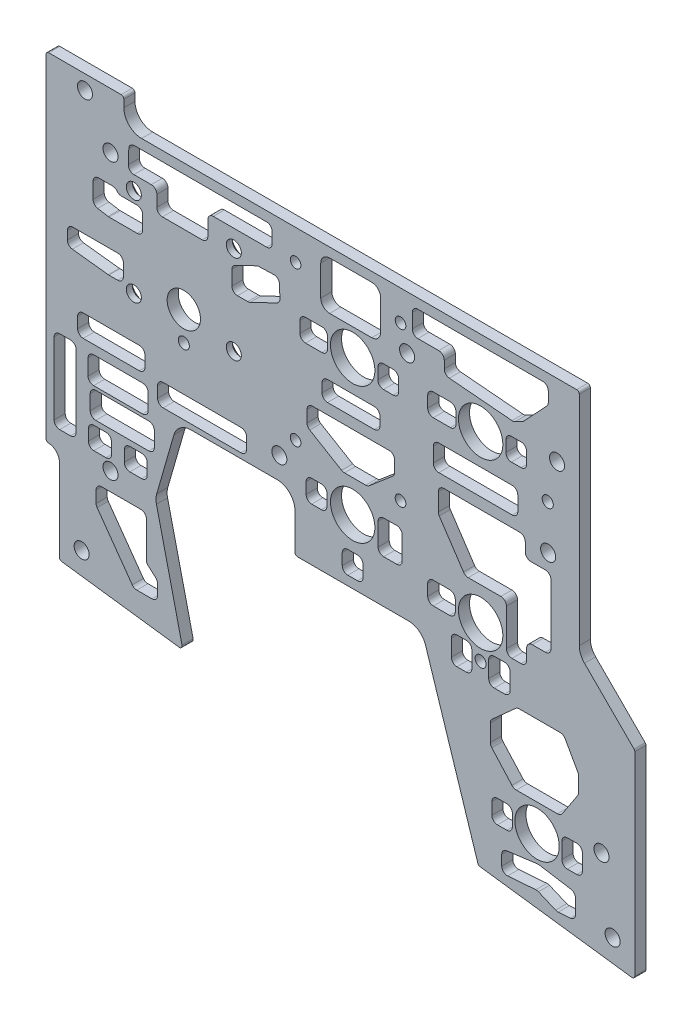
SolidWorks part; units mm, degrees
ref_plane "Front Plane" through (0, 0, 0) normal (0, 0, 1) x (1, 0, 0)
ref_plane "Top Plane" through (0, 0, 0) normal (0, 1, 0) x (1, 0, 0)
ref_plane "Right Plane" through (0, 0, 0) normal (1, 0, 0) x (0, 0, -1)
sketch "Sketch1" plane through (0, 0, 0) normal (0, 0, 1) x (1, 0, 0)
  line L16 (3.81, -91.8845) -> (3.81, -115.4033)
  line L17 (4.4725, -116.1588) -> (38.0231, -120.5758)
  line L18 (38.8645, -119.6465) -> (31.5446, -88.4134)
  line L19 (31.6093, -85.8475) -> (36.5334, -68.7608)
  line L20 (41.4148, -65.0875) -> (66.04, -65.0875)
  line L21 (71.12, -70.1675) -> (71.12, -80.518)
  line L22 (71.882, -81.28) -> (103.6122, -81.28)
  line L23 (108.4484, -84.805) -> (123.4233, -131.3792)
  line L24 (124.0493, -131.9014) -> (167.4135, -137.6104)
  line L25 (168.275, -136.8549) -> (168.275, -81.3036)
  line L26 (168.0518, -80.7647) -> (153.8879, -66.6008)
  line L27 (152.4, -63.0087) -> (152.4, -0.762)
  line L28 (151.638, 0) -> (27.305, 0)
  line L29 (22.225, 5.08) -> (22.225, 7.1755)
  line L30 (21.463, 7.9375) -> (0.762, 7.9375)
  line L31 (0, 7.1755) -> (0, -87.9495)
  line L32 (3.81, -91.8845) -> (3.81, -115.4033)
  line L33 (4.4725, -116.1588) -> (38.0231, -120.5758)
  line L34 (38.8645, -119.6465) -> (31.5446, -88.4134)
  line L35 (31.6093, -85.8475) -> (36.5334, -68.7608)
  line L36 (41.4148, -65.0875) -> (66.04, -65.0875)
  line L37 (71.12, -70.1675) -> (71.12, -80.518)
  line L38 (71.882, -81.28) -> (103.6122, -81.28)
  line L39 (108.4484, -84.805) -> (123.4233, -131.3792)
  line L40 (124.0493, -131.9014) -> (167.4135, -137.6104)
  line L41 (168.275, -136.8549) -> (168.275, -81.3036)
  line L42 (168.0518, -80.7647) -> (153.8879, -66.6008)
  line L43 (152.4, -63.0087) -> (152.4, -0.762)
  line L44 (151.638, 0) -> (27.305, 0)
  line L45 (22.225, 5.08) -> (22.225, 7.1755)
  line L46 (21.463, 7.9375) -> (0.762, 7.9375)
  line L47 (0, 7.1755) -> (0, -87.9495)
  arc A17 (3.81, -91.8845) -> (0.7374, -88.7112) centre (0.635, -91.8845) ccw
  arc A18 (3.81, -115.4033) -> (4.4725, -116.1588) centre (4.572, -115.4033) ccw
  arc A19 (38.0231, -120.5758) -> (38.8645, -119.6465) centre (38.1226, -119.8204) ccw
  arc A20 (31.6093, -85.8475) -> (31.5446, -88.4134) centre (36.4906, -87.2542) ccw
  arc A21 (41.4148, -65.0875) -> (36.5334, -68.7608) centre (41.4148, -70.1675) ccw
  arc A22 (71.12, -70.1675) -> (66.04, -65.0875) centre (66.04, -70.1675) ccw
  arc A23 (71.12, -80.518) -> (71.882, -81.28) centre (71.882, -80.518) ccw
  arc A24 (108.4484, -84.805) -> (103.6122, -81.28) centre (103.6122, -86.36) ccw
  arc A25 (123.4233, -131.3792) -> (124.0493, -131.9014) centre (124.1487, -131.1459) ccw
  arc A26 (167.4135, -137.6104) -> (168.275, -136.8549) centre (167.513, -136.8549) ccw
  arc A27 (168.275, -81.3036) -> (168.0518, -80.7647) centre (167.513, -81.3036) ccw
  arc A28 (152.4, -63.0087) -> (153.8879, -66.6008) centre (157.48, -63.0087) ccw
  arc A29 (152.4, -0.762) -> (151.638, 0) centre (151.638, -0.762) ccw
  arc A30 (22.225, 5.08) -> (27.305, 0) centre (27.305, 5.08) ccw
  arc A31 (22.225, 7.1755) -> (21.463, 7.9375) centre (21.463, 7.1755) ccw
  arc A32 (0.762, 7.9375) -> (0, 7.1755) centre (0.762, 7.1755) ccw
  arc A33 (0, -87.9495) -> (0.7374, -88.7112) centre (0.762, -87.9495) ccw
  arc A34 (3.81, -91.8845) -> (0.7374, -88.7112) centre (0.635, -91.8845) ccw
  arc A35 (3.81, -115.4033) -> (4.4725, -116.1588) centre (4.572, -115.4033) ccw
  arc A36 (38.0231, -120.5758) -> (38.8645, -119.6465) centre (38.1226, -119.8204) ccw
  arc A37 (31.6093, -85.8475) -> (31.5446, -88.4134) centre (36.4906, -87.2542) ccw
  arc A38 (41.4148, -65.0875) -> (36.5334, -68.7608) centre (41.4148, -70.1675) ccw
  arc A39 (71.12, -70.1675) -> (66.04, -65.0875) centre (66.04, -70.1675) ccw
  arc A40 (71.12, -80.518) -> (71.882, -81.28) centre (71.882, -80.518) ccw
  arc A41 (108.4484, -84.805) -> (103.6122, -81.28) centre (103.6122, -86.36) ccw
  arc A42 (123.4233, -131.3792) -> (124.0493, -131.9014) centre (124.1487, -131.1459) ccw
  arc A43 (167.4135, -137.6104) -> (168.275, -136.8549) centre (167.513, -136.8549) ccw
  arc A44 (168.275, -81.3036) -> (168.0518, -80.7647) centre (167.513, -81.3036) ccw
  arc A45 (152.4, -63.0087) -> (153.8879, -66.6008) centre (157.48, -63.0087) ccw
  arc A46 (152.4, -0.762) -> (151.638, 0) centre (151.638, -0.762) ccw
  arc A47 (22.225, 5.08) -> (27.305, 0) centre (27.305, 5.08) ccw
  arc A48 (22.225, 7.1755) -> (21.463, 7.9375) centre (21.463, 7.1755) ccw
  arc A49 (0.762, 7.9375) -> (0, 7.1755) centre (0.762, 7.1755) ccw
  arc A50 (0, -87.9495) -> (0.7374, -88.7112) centre (0.762, -87.9495) ccw
  dimension "D1" = 0
extrude "Boss-Extrude1" add sketch "Sketch1" against normal blind 3.175
hole_wizard "#6 Clearance Hole1" positions "Sketch3" profile "Sketch2" hole size "#6" standard "ANSI Inch" end condition through all
sketch "Sketch3" plane through (0, 0, -3.175) normal (0, 0, -1) x (-1, 0, 0)
  point P0 (-11.1125, 3.81)
  point P3 (-18.415, -7.9375)
  point P6 (-103.1875, -15.24)
  point P9 (-143.51, -44.45)
  point P12 (-158.75, -111.125)
  point P15 (-18.415, -86.741)
  point P18 (-66.675, -58.7375)
  point P21 (-10.16, -110.5028)
  point P25 (-146.05, -20.6375)
  point P28 (-161.925, -130.483)
sketch "Sketch2" plane through (11.1125, 3.81, -3.175) normal (1, 0, 0) x (0, 1, 0)
  line L0 (0, 0) -> (0, 3.175)
  line L1 (0, 3.175) -> (2.1526, 3.175)
  line L2 (2.1526, 3.175) -> (2.1526, 0)
  line L5 (2.1526, 0) -> (0, 0)
  line L11 (0, -6.35) -> (0, 107.95) construction
  dimension "Thru Hole Dia." = 4.3053
  dimension "Thru Hole Depth" = 3.175
sketch "Sketch4" plane through (0, 0, -3.175) normal (0, 0, -1) x (-1, 0, 0)
  circle A0 centre (-140.335, -115.57) radius 6.35
  circle A1 centre (-124.206, -71.4375) radius 6.35
  circle A2 centre (-87.63, -62.992) radius 6.35
  circle A3 centre (-87.63, -24.13) radius 6.35
  circle A4 centre (-124.206, -24.13) radius 6.35
  circle A5 centre (-124.206, -80.9625) radius 1.5875
  circle A6 centre (-39.37, -36.322) radius 4.7625
  dimension "D1" = 12.7
  dimension "D2" = 3.175
  dimension "D4" = 9.525
  dimension "D3" = 9.525
extrude "Cut-Extrude1" cut sketch "Sketch4" against normal through all
hole_wizard "CSK for #6 Flat Head Machine Screw (100)1" positions "Sketch6" profile "Sketch5" countersink size "#6" standard "ANSI Inch" end condition through all
sketch "Sketch6" plane through (0, 0, -3.175) normal (0, 0, -1) x (-1, 0, 0)
  point P0 (-53.6575, -14.097)
  point P2 (-25.0825, -14.097)
  point P4 (-25.0825, -39.497)
  point P6 (-53.6575, -39.497)
sketch "Sketch5" plane through (53.6575, -14.097, -3.175) normal (1, 0, 0) x (0, 1, 0)
  line L0 (0, 0) -> (0, 3.175)
  line L1 (0, 3.175) -> (2.1526, 3.175)
  line L2 (2.1526, 3.175) -> (2.1526, 1.4209)
  line L3 (2.1526, 1.4209) -> (3.846, 0)
  line L5 (3.846, 0) -> (0, 0)
  line L6 (-2.1526, 1.4209) -> (-3.846, 0) construction
  line L11 (0, -6.35) -> (0, 107.95) construction
  dimension "Thru Hole Dia." = 4.3053
  dimension "Thru Hole Depth" = 3.175
  dimension "Near C'Sink Dia." = 7.692
  dimension "Near C'Sink Angle" = 100
hole_wizard "#0 Clearance Hole1" positions "Sketch7" profile "Sketch8" hole size "#0" standard "ANSI Inch" end condition through all
sketch "Sketch7" plane through (0, 0, -9.525) normal (0, 0, -1) x (-1, 0, 0)
  point P0 (-39.37, -44.577)
sketch "Sketch8" plane through (39.37, -44.577, -9.525) normal (1, 0, 0) x (0, 1, 0)
  line L0 (0, 0) -> (0, 9.525)
  line L1 (0, 9.525) -> (0.9271, 9.525)
  line L2 (0.9271, 9.525) -> (0.9271, 0)
  line L3 (0.9271, 0) -> (0, 0)
  line L4 (0, -6.35) -> (0, 107.95) construction
  dimension "Thru Hole Dia." = 1.8542
  dimension "Thru Hole Depth" = 9.525
hole_wizard "1/8 (0.125) Diameter Hole1" positions "Sketch9" profile "Sketch10" hole size "1/8" standard "ANSI Inch" end condition through all
sketch "Sketch9" plane through (0, 0, 0) normal (0, 0, 1) x (1, 0, 0)
  point P0 (39.37, -44.577)
sketch "Sketch10" plane through (39.37, -44.577, 0) normal (1, 0, 0) x (0, -1, 0)
  line L0 (0, 0) -> (0, 3.175)
  line L1 (0, 3.175) -> (1.5875, 3.175)
  line L2 (1.5875, 3.175) -> (1.5875, 0)
  line L5 (1.5875, 0) -> (0, 0)
  line L11 (0, -6.35) -> (0, 107.95) construction
  dimension "Thru Hole Dia." = 3.175
  dimension "Thru Hole Depth" = 3.175
sketch "Sketch17" plane through (0, 0, 0) normal (0, 0, -1) x (-1, 0, 0)
  line L0 (-141.9544, -2.7948) -> (-106.2662, -2.7948)
  line L1 (-104.6787, -4.3823) -> (-104.6787, -8.4606)
  line L2 (-106.2662, -10.0481) -> (-112.2209, -10.0481)
  line L3 (-113.8084, -11.6356) -> (-113.8084, -13.7762)
  line L4 (-115.259, -15.3578) -> (-133.159, -16.9076)
  line L5 (-134.0131, -16.7423) -> (-136.0874, -15.6921)
  line L6 (-136.5298, -15.36) -> (-143.114, -8.3185)
  line L7 (-143.5419, -7.2342) -> (-143.5419, -4.3823)
  line L8 (-93.0669, -2.7076) -> (-81.0441, -2.7076)
  line L9 (-78.5041, -5.2476) -> (-78.5041, -13.8956)
  line L10 (-81.0441, -16.4356) -> (-93.0669, -16.4356)
  line L11 (-95.6069, -13.8956) -> (-95.6069, -5.2476)
  line L12 (-72.5612, -22.437) -> (-72.5612, -25.637)
  line L13 (-74.1487, -27.2245) -> (-78.851, -27.2245)
  line L14 (-80.4385, -25.637) -> (-80.4385, -22.437)
  line L15 (-74.1487, -20.8495) -> (-78.851, -20.8495)
  line L16 (-99.2018, -21.1963) -> (-96.4213, -21.1963)
  line L17 (-94.8338, -22.7838) -> (-94.8338, -25.9818)
  line L18 (-96.4213, -27.5693) -> (-99.2018, -27.5693)
  line L19 (-100.7893, -25.9818) -> (-100.7893, -22.7838)
  line L20 (-109.0792, -22.6549) -> (-109.0792, -25.8549)
  line L21 (-110.6667, -27.4424) -> (-115.5536, -27.4424)
  line L22 (-117.1411, -25.8549) -> (-117.1411, -22.6549)
  line L23 (-110.6667, -21.0674) -> (-115.5536, -21.0674)
  line L24 (-135.7738, -20.8814) -> (-132.9933, -20.8814)
  line L25 (-131.4058, -22.4689) -> (-131.4058, -25.667)
  line L26 (-132.9933, -27.2545) -> (-135.7738, -27.2545)
  line L27 (-137.3613, -25.667) -> (-137.3613, -22.4689)
  line L28 (-93.8189, -33.0853) -> (-80.4385, -33.0853)
  line L29 (-78.851, -34.6728) -> (-78.851, -37.1954)
  line L30 (-80.4385, -38.7829) -> (-93.8189, -38.7829)
  line L31 (-95.4064, -34.6728) -> (-95.4064, -37.1954)
  line L32 (-133.2346, -32.9063) -> (-112.2542, -32.9063)
  line L33 (-110.6667, -34.4938) -> (-110.6667, -38.6545)
  line L34 (-112.2542, -40.242) -> (-133.2346, -40.242)
  line L35 (-134.8221, -38.6545) -> (-134.8221, -34.4938)
  line L36 (-98.0498, -41.8469) -> (-76.1717, -41.8469)
  line L37 (-74.5842, -43.4344) -> (-74.5842, -46.7771)
  line L38 (-75.3596, -48.1412) -> (-84.4657, -53.5626)
  line L39 (-85.2778, -53.7861) -> (-91.3474, -53.7861)
  line L40 (-92.3756, -53.4081) -> (-99.0779, -47.711)
  line L41 (-99.6373, -46.5014) -> (-99.6373, -43.4344)
  line L42 (-135.3789, -43.4344) -> (-113.699, -43.4344)
  line L43 (-112.1115, -45.0219) -> (-112.1115, -50.0429)
  line L44 (-112.3789, -50.9245) -> (-119.3229, -61.3222)
  line L45 (-120.6431, -62.0281) -> (-129.9871, -62.0281)
  line L47 (-136.9664, -47.5212) -> (-136.9664, -45.0219)
  line L48 (-55.7285, -57.3176) -> (-33.4587, -57.3176)
  line L49 (-31.8712, -58.9051) -> (-31.8712, -62.02)
  line L50 (-33.4587, -63.6075) -> (-55.7285, -63.6075)
  line L51 (-57.316, -62.02) -> (-57.316, -58.9051)
  line L52 (-78.7021, -59.8174) -> (-75.9216, -59.8174)
  line L53 (-74.3341, -61.4049) -> (-74.3341, -64.603)
  line L54 (-75.9216, -66.1905) -> (-78.7021, -66.1905)
  line L55 (-80.2896, -64.603) -> (-80.2896, -61.4049)
  line L56 (-89.0189, -72.2548) -> (-86.2384, -72.2548)
  line L57 (-84.6509, -73.8423) -> (-84.6509, -77.0403)
  line L58 (-86.2384, -78.6278) -> (-89.0189, -78.6278)
  line L59 (-90.6064, -77.0403) -> (-90.6064, -73.8423)
  line L60 (-109.0756, -69.248) -> (-109.0756, -72.448)
  line L61 (-110.6631, -74.0355) -> (-115.3654, -74.0355)
  line L62 (-116.9529, -72.448) -> (-116.9529, -69.248)
  line L63 (-110.6631, -67.6605) -> (-115.3654, -67.6605)
  line L64 (-148.3701, -88.0766) -> (-151.9572, -94.4661)
  line L65 (-152.1698, -95.2794) -> (-152.1698, -99.4916)
  line L66 (-151.8961, -100.4052) -> (-147.5598, -106.9917)
  line L67 (-138.5539, -49.1087) -> (-142.7058, -49.1087)
  line L68 (-146.1721, -107.7395) -> (-134.3926, -107.7395)
  line L69 (-144.2933, -50.6962) -> (-144.2933, -67.8867)
  line L70 (-133.1575, -107.1893) -> (-127.3956, -100.785)
  line L71 (-126.9693, -99.6738) -> (-126.9693, -94.8668)
  line L72 (-127.5195, -93.6317) -> (-134.1629, -87.6548)
  line L73 (-135.2742, -87.2285) -> (-146.9213, -87.2285)
  line L74 (-137.3613, -71.0617) -> (-137.3613, -74.1715)
  line L75 (-135.7738, -75.759) -> (-133.1621, -75.759)
  line L76 (-131.5746, -74.1715) -> (-131.5746, -63.6156)
  line L78 (-132.6264, -79.3569) -> (-132.6264, -84.055)
  line L79 (-131.0389, -85.6425) -> (-128.0874, -85.6425)
  line L80 (-126.4999, -84.055) -> (-126.4999, -79.3653)
  line L81 (-128.0829, -77.7778) -> (-131.0344, -77.7694)
  line L82 (-121.6938, -79.414) -> (-121.6938, -84.1113)
  line L83 (-120.1063, -85.6988) -> (-117.4258, -85.6988)
  line L84 (-115.8383, -84.1113) -> (-115.8383, -79.4216)
  line L85 (-117.4212, -77.8341) -> (-120.1018, -77.8265)
  line L86 (-101.7978, -60.9375) -> (-101.7978, -67.3473)
  line L87 (-100.2103, -68.9348) -> (-96.4976, -68.9348)
  line L88 (-94.9101, -67.3473) -> (-94.9101, -60.9481)
  line L89 (-96.4931, -59.3606) -> (-100.2058, -59.35)
  line L90 (-153.2801, -113.8454) -> (-153.2801, -118.4115)
  line L91 (-151.6926, -119.999) -> (-149.0121, -119.999)
  line L92 (-147.4246, -118.4115) -> (-147.4246, -113.853)
  line L93 (-149.0076, -112.2655) -> (-151.6881, -112.2579)
  line L94 (-133.2696, -114.0603) -> (-133.2696, -117.4522)
  line L95 (-131.6821, -119.0397) -> (-129.0016, -119.0397)
  line L96 (-127.4141, -117.4522) -> (-127.4141, -114.0679)
  line L97 (-128.997, -112.4804) -> (-131.6776, -112.4728)
  line L98 (-150.0084, -124.4751) -> (-140.8902, -122.9925)
  line L99 (-140.4256, -122.9858) -> (-131.6139, -124.1607)
  line L100 (-130.2362, -125.7343) -> (-130.2362, -128.6297)
  line L101 (-131.9392, -130.213) -> (-139.9781, -129.6268)
  line L102 (-140.7126, -129.7482) -> (-145.6471, -131.838)
  line L103 (-146.3817, -131.9595) -> (-149.8691, -131.7052)
  line L104 (-151.3411, -130.1219) -> (-151.3411, -126.042)
  line L105 (-63.0404, -2.7948) -> (-25.2277, -2.7948)
  line L106 (-23.641, -4.3315) -> (-23.5105, -8.4099)
  line L107 (-25.0972, -10.0481) -> (-30.0725, -10.0481)
  line L108 (-31.66, -11.6356) -> (-31.66, -14.8481)
  line L109 (-33.2475, -16.4356) -> (-44.6401, -16.4356)
  line L110 (-46.2276, -14.8481) -> (-46.2276, -10.6224)
  line L111 (-47.8151, -9.0349) -> (-63.0404, -9.0349)
  line L112 (-64.6279, -7.4474) -> (-64.6279, -4.3823)
  line L113 (-14.7591, -23.5708) -> (-17.7234, -24.0903)
  line L114 (-17.9974, -24.1142) -> (-26.0381, -24.1142)
  line L115 (-27.6256, -22.5267) -> (-27.6256, -18.7366)
  line L116 (-26.0381, -17.1491) -> (-21.5632, -17.1491)
  line L117 (-20.4504, -16.6939) -> (-20.1204, -16.3695)
  line L118 (-19.0076, -15.9142) -> (-15.0331, -15.9142)
  line L119 (-13.4456, -17.5017) -> (-13.4456, -22.0071)
  line L120 (-7.6875, -31.7843) -> (-20.4927, -31.7843)
  line L121 (-22.0802, -33.3718) -> (-22.0802, -36.9105)
  line L122 (-20.4927, -38.498) -> (-17.9504, -38.498)
  line L123 (-17.7686, -38.4875) -> (-7.5058, -37.3048)
  line L124 (-6.1, -35.7277) -> (-6.1, -33.3718)
  line L125 (-54.0177, -18.0353) -> (-60.157, -15.0963)
  line L126 (-60.7931, -14.9415) -> (-65.0805, -14.8081)
  line L127 (-66.7166, -16.3454) -> (-66.8282, -19.9294)
  line L128 (-65.9269, -21.4107) -> (-58.3022, -25.0607)
  line L129 (-57.6167, -25.2163) -> (-54.7032, -25.2163)
  line L130 (-53.1157, -23.6288) -> (-53.1157, -19.4672)
  line L131 (-24.6224, -111.8142) -> (-14.5986, -97.7476)
  line L132 (-14.304, -96.8263) -> (-14.304, -93.5113)
  line L133 (-2.2976, -61.6269) -> (-2.2976, -82.1859)
  line L134 (-3.8851, -83.7734) -> (-6.9926, -83.7734)
  line L135 (-8.5801, -82.1859) -> (-8.5801, -61.6269)
  line L136 (-6.9926, -60.0394) -> (-3.8851, -60.0394)
  line L137 (-15.8915, -91.9238) -> (-27.0858, -91.9238)
  line L138 (-28.6733, -93.5113) -> (-28.6733, -103.656)
  line L139 (-29.2117, -104.8474) -> (-31.3328, -106.7152)
  line L140 (-31.8712, -107.9067) -> (-31.8712, -110.8929)
  line L141 (-30.2837, -112.4804) -> (-25.9153, -112.4804)
  line L142 (-26.655, -51.5392) -> (-10.6039, -51.5392)
  line L143 (-9.0164, -53.1267) -> (-9.0164, -56.2416)
  line L144 (-10.6039, -57.8291) -> (-26.655, -57.8291)
  line L145 (-28.2425, -56.2416) -> (-28.2425, -53.1267)
  line L146 (-27.6052, -60.385) -> (-13.5866, -60.385)
  line L147 (-11.9991, -61.9725) -> (-11.9991, -66.4544)
  line L148 (-13.5866, -68.0419) -> (-27.6052, -68.0419)
  line L149 (-29.1927, -66.4544) -> (-29.1927, -61.9725)
  line L150 (-29.347, -68.9032) -> (-14.2014, -68.9032)
  line L151 (-12.6139, -70.4907) -> (-12.6139, -74.7412)
  line L152 (-14.2014, -76.3287) -> (-29.347, -76.3287)
  line L153 (-30.9345, -74.7412) -> (-30.9345, -70.4907)
  line L154 (-27.3287, -77.9076) -> (-23.9481, -77.9076)
  line L155 (-22.3606, -79.4951) -> (-22.3606, -82.61)
  line L156 (-23.9481, -84.1975) -> (-27.3287, -84.1975)
  line L157 (-28.9162, -82.61) -> (-28.9162, -79.4951)
  line L158 (-17.1192, -77.821) -> (-13.667, -77.821)
  line L159 (-12.0795, -79.4085) -> (-12.0795, -82.5234)
  line L160 (-13.667, -84.1109) -> (-17.1192, -84.1109)
  line L161 (-18.7067, -82.5234) -> (-18.7067, -79.4085)
  line L162 (-142.7058, -69.4742) -> (-138.9488, -69.4742)
  arc A0 (-106.2662, -2.7948) -> (-104.6787, -4.3823) centre (-106.2662, -4.3823) cw
  arc A1 (-104.6787, -8.4606) -> (-106.2662, -10.0481) centre (-106.2662, -8.4606) cw
  arc A2 (-112.2209, -10.0481) -> (-113.8084, -11.6356) centre (-112.2209, -11.6356) ccw
  arc A3 (-113.8084, -13.7762) -> (-115.259, -15.3578) centre (-115.3959, -13.7762) cw
  arc A4 (-133.159, -16.9076) -> (-134.0131, -16.7423) centre (-133.296, -15.326) cw
  arc A5 (-136.0874, -15.6921) -> (-136.5298, -15.36) centre (-135.3703, -14.2758) cw
  arc A6 (-143.114, -8.3185) -> (-143.5419, -7.2342) centre (-141.9544, -7.2342) cw
  arc A7 (-141.9544, -2.7948) -> (-143.5419, -4.3823) centre (-141.9544, -4.3823) ccw
  arc A8 (-81.0441, -2.7076) -> (-78.5041, -5.2476) centre (-81.0441, -5.2476) cw
  arc A9 (-78.5041, -13.8956) -> (-81.0441, -16.4356) centre (-81.0441, -13.8956) cw
  arc A10 (-93.0669, -16.4356) -> (-95.6069, -13.8956) centre (-93.0669, -13.8956) cw
  arc A11 (-93.0669, -2.7076) -> (-95.6069, -5.2476) centre (-93.0669, -5.2476) ccw
  arc A12 (-72.5612, -22.437) -> (-74.1487, -20.8495) centre (-74.1487, -22.437) ccw
  arc A13 (-72.5612, -25.637) -> (-74.1487, -27.2245) centre (-74.1487, -25.637) cw
  arc A14 (-78.851, -27.2245) -> (-80.4385, -25.637) centre (-78.851, -25.637) cw
  arc A15 (-80.4385, -22.437) -> (-78.851, -20.8495) centre (-78.851, -22.437) cw
  arc A16 (-96.4213, -21.1963) -> (-94.8338, -22.7838) centre (-96.4213, -22.7838) cw
  arc A17 (-94.8338, -25.9818) -> (-96.4213, -27.5693) centre (-96.4213, -25.9818) cw
  arc A18 (-99.2018, -27.5693) -> (-100.7893, -25.9818) centre (-99.2018, -25.9818) cw
  arc A19 (-99.2018, -21.1963) -> (-100.7893, -22.7838) centre (-99.2018, -22.7838) ccw
  arc A20 (-109.0792, -22.6549) -> (-110.6667, -21.0674) centre (-110.6667, -22.6549) ccw
  arc A21 (-109.0792, -25.8549) -> (-110.6667, -27.4424) centre (-110.6667, -25.8549) cw
  arc A22 (-115.5536, -27.4424) -> (-117.1411, -25.8549) centre (-115.5536, -25.8549) cw
  arc A23 (-117.1411, -22.6549) -> (-115.5536, -21.0674) centre (-115.5536, -22.6549) cw
  arc A24 (-132.9933, -20.8814) -> (-131.4058, -22.4689) centre (-132.9933, -22.4689) cw
  arc A25 (-131.4058, -25.667) -> (-132.9933, -27.2545) centre (-132.9933, -25.667) cw
  arc A26 (-135.7738, -27.2545) -> (-137.3613, -25.667) centre (-135.7738, -25.667) cw
  arc A27 (-135.7738, -20.8814) -> (-137.3613, -22.4689) centre (-135.7738, -22.4689) ccw
  arc A28 (-80.4385, -33.0853) -> (-78.851, -34.6728) centre (-80.4385, -34.6728) cw
  arc A29 (-78.851, -37.1954) -> (-80.4385, -38.7829) centre (-80.4385, -37.1954) cw
  arc A30 (-93.8189, -38.7829) -> (-95.4064, -37.1954) centre (-93.8189, -37.1954) cw
  arc A31 (-93.8189, -33.0853) -> (-95.4064, -34.6728) centre (-93.8189, -34.6728) ccw
  arc A32 (-112.2542, -32.9063) -> (-110.6667, -34.4938) centre (-112.2542, -34.4938) cw
  arc A33 (-110.6667, -38.6545) -> (-112.2542, -40.242) centre (-112.2542, -38.6545) cw
  arc A34 (-133.2346, -40.242) -> (-134.8221, -38.6545) centre (-133.2346, -38.6545) cw
  arc A35 (-133.2346, -32.9063) -> (-134.8221, -34.4938) centre (-133.2346, -34.4938) ccw
  arc A36 (-91.3474, -53.7861) -> (-92.3756, -53.4081) centre (-91.3474, -52.1986) cw
  arc A37 (-84.4657, -53.5626) -> (-85.2778, -53.7861) centre (-85.2778, -52.1986) cw
  arc A38 (-74.5842, -46.7771) -> (-75.3596, -48.1412) centre (-76.1717, -46.7771) cw
  arc A39 (-76.1717, -41.8469) -> (-74.5842, -43.4344) centre (-76.1717, -43.4344) cw
  arc A40 (-98.0498, -41.8469) -> (-99.6373, -43.4344) centre (-98.0498, -43.4344) ccw
  arc A41 (-99.0779, -47.711) -> (-99.6373, -46.5014) centre (-98.0498, -46.5014) cw
  arc A42 (-113.699, -43.4344) -> (-112.1115, -45.0219) centre (-113.699, -45.0219) cw
  arc A43 (-112.1115, -50.0429) -> (-112.3789, -50.9245) centre (-113.699, -50.0429) cw
  arc A44 (-119.3229, -61.3222) -> (-120.6431, -62.0281) centre (-120.6431, -60.4406) cw
  arc A47 (-135.3789, -43.4344) -> (-136.9664, -45.0219) centre (-135.3789, -45.0219) ccw
  arc A48 (-33.4587, -57.3176) -> (-31.8712, -58.9051) centre (-33.4587, -58.9051) cw
  arc A49 (-31.8712, -62.02) -> (-33.4587, -63.6075) centre (-33.4587, -62.02) cw
  arc A50 (-55.7285, -63.6075) -> (-57.316, -62.02) centre (-55.7285, -62.02) cw
  arc A51 (-55.7285, -57.3176) -> (-57.316, -58.9051) centre (-55.7285, -58.9051) ccw
  arc A52 (-75.9216, -59.8174) -> (-74.3341, -61.4049) centre (-75.9216, -61.4049) cw
  arc A53 (-74.3341, -64.603) -> (-75.9216, -66.1905) centre (-75.9216, -64.603) cw
  arc A54 (-78.7021, -66.1905) -> (-80.2896, -64.603) centre (-78.7021, -64.603) cw
  arc A55 (-78.7021, -59.8174) -> (-80.2896, -61.4049) centre (-78.7021, -61.4049) ccw
  arc A56 (-86.2384, -72.2548) -> (-84.6509, -73.8423) centre (-86.2384, -73.8423) cw
  arc A57 (-84.6509, -77.0403) -> (-86.2384, -78.6278) centre (-86.2384, -77.0403) cw
  arc A58 (-89.0189, -78.6278) -> (-90.6064, -77.0403) centre (-89.0189, -77.0403) cw
  arc A59 (-89.0189, -72.2548) -> (-90.6064, -73.8423) centre (-89.0189, -73.8423) ccw
  arc A60 (-109.0756, -69.248) -> (-110.6631, -67.6605) centre (-110.6631, -69.248) ccw
  arc A61 (-109.0756, -72.448) -> (-110.6631, -74.0355) centre (-110.6631, -72.448) cw
  arc A62 (-115.3654, -74.0355) -> (-116.9529, -72.448) centre (-115.3654, -72.448) cw
  arc A63 (-116.9529, -69.248) -> (-115.3654, -67.6605) centre (-115.3654, -69.248) cw
  arc A64 (-134.1629, -87.6548) -> (-135.2742, -87.2285) centre (-135.2742, -88.8899) ccw
  arc A65 (-126.9693, -94.8668) -> (-127.5195, -93.6317) centre (-128.6308, -94.8668) ccw
  arc A66 (-127.3956, -100.785) -> (-126.9693, -99.6738) centre (-128.6308, -99.6738) ccw
  arc A67 (-134.3926, -107.7395) -> (-133.1575, -107.1893) centre (-134.3926, -106.0781) ccw
  arc A68 (-147.5598, -106.9917) -> (-146.1721, -107.7395) centre (-146.1721, -106.0781) ccw
  arc A69 (-152.1698, -99.4916) -> (-151.8961, -100.4052) centre (-150.5084, -99.4916) ccw
  arc A70 (-151.9572, -94.4661) -> (-152.1698, -95.2794) centre (-150.5084, -95.2794) ccw
  arc A71 (-148.3701, -88.0766) -> (-146.9213, -87.2285) centre (-146.9213, -88.8899) cw
  arc A74 (-133.1621, -75.759) -> (-131.5746, -74.1715) centre (-133.1621, -74.1715) ccw
  arc A75 (-137.3613, -74.1715) -> (-135.7738, -75.759) centre (-135.7738, -74.1715) ccw
  arc A76 (-132.6264, -79.3569) -> (-131.0344, -77.7694) centre (-131.0389, -79.3569) cw
  arc A77 (-126.4999, -79.3653) -> (-128.0829, -77.7778) centre (-128.0874, -79.3653) ccw
  arc A78 (-128.0874, -85.6425) -> (-126.4999, -84.055) centre (-128.0874, -84.055) ccw
  arc A79 (-132.6264, -84.055) -> (-131.0389, -85.6425) centre (-131.0389, -84.055) ccw
  arc A80 (-121.6938, -79.414) -> (-120.1018, -77.8265) centre (-120.1063, -79.414) cw
  arc A81 (-115.8383, -79.4216) -> (-117.4212, -77.8341) centre (-117.4258, -79.4216) ccw
  arc A82 (-117.4258, -85.6988) -> (-115.8383, -84.1113) centre (-117.4258, -84.1113) ccw
  arc A83 (-121.6938, -84.1113) -> (-120.1063, -85.6988) centre (-120.1063, -84.1113) ccw
  arc A84 (-101.7978, -60.9375) -> (-100.2058, -59.35) centre (-100.2103, -60.9375) cw
  arc A85 (-94.9101, -60.9481) -> (-96.4931, -59.3606) centre (-96.4976, -60.9481) ccw
  arc A86 (-96.4976, -68.9348) -> (-94.9101, -67.3473) centre (-96.4976, -67.3473) ccw
  arc A87 (-101.7978, -67.3473) -> (-100.2103, -68.9348) centre (-100.2103, -67.3473) ccw
  arc A88 (-153.2801, -113.8454) -> (-151.6881, -112.2579) centre (-151.6926, -113.8454) cw
  arc A89 (-147.4246, -113.853) -> (-149.0076, -112.2655) centre (-149.0121, -113.853) ccw
  arc A90 (-149.0121, -119.999) -> (-147.4246, -118.4115) centre (-149.0121, -118.4115) ccw
  arc A91 (-153.2801, -118.4115) -> (-151.6926, -119.999) centre (-151.6926, -118.4115) ccw
  arc A92 (-133.2696, -114.0603) -> (-131.6776, -112.4728) centre (-131.6821, -114.0603) cw
  arc A93 (-127.4141, -114.0679) -> (-128.997, -112.4804) centre (-129.0016, -114.0679) ccw
  arc A94 (-129.0016, -119.0397) -> (-127.4141, -117.4522) centre (-129.0016, -117.4522) ccw
  arc A95 (-133.2696, -117.4522) -> (-131.6821, -119.0397) centre (-131.6821, -117.4522) ccw
  arc A96 (-140.8902, -122.9925) -> (-140.4256, -122.9858) centre (-140.6354, -124.5594) cw
  arc A97 (-131.6139, -124.1607) -> (-130.2362, -125.7343) centre (-131.8237, -125.7343) cw
  arc A98 (-130.2362, -128.6297) -> (-131.9392, -130.213) centre (-131.8237, -128.6297) cw
  arc A99 (-139.9781, -129.6268) -> (-140.7126, -129.7482) centre (-140.0935, -131.2101) ccw
  arc A100 (-145.6471, -131.838) -> (-146.3817, -131.9595) centre (-146.2662, -130.3762) cw
  arc A101 (-149.8691, -131.7052) -> (-151.3411, -130.1219) centre (-149.7536, -130.1219) cw
  arc A102 (-150.0084, -124.4751) -> (-151.3411, -126.042) centre (-149.7536, -126.042) ccw
  arc A103 (-63.0404, -2.7948) -> (-64.6279, -4.3823) centre (-63.0404, -4.3823) ccw
  arc A104 (-25.2277, -2.7948) -> (-23.641, -4.3315) centre (-25.2277, -4.3823) cw
  arc A105 (-23.5105, -8.4099) -> (-25.0972, -10.0481) centre (-25.0972, -8.4606) cw
  arc A106 (-30.0725, -10.0481) -> (-31.66, -11.6356) centre (-30.0725, -11.6356) ccw
  arc A107 (-31.66, -14.8481) -> (-33.2475, -16.4356) centre (-33.2475, -14.8481) cw
  arc A108 (-44.6401, -16.4356) -> (-46.2276, -14.8481) centre (-44.6401, -14.8481) cw
  arc A109 (-46.2276, -10.6224) -> (-47.8151, -9.0349) centre (-47.8151, -10.6224) ccw
  arc A110 (-63.0404, -9.0349) -> (-64.6279, -7.4474) centre (-63.0404, -7.4474) cw
  arc A111 (-23.9481, -77.9076) -> (-22.3606, -79.4951) centre (-23.9481, -79.4951) cw
  arc A112 (-21.5632, -17.1491) -> (-20.4504, -16.6939) centre (-21.5632, -15.5616) ccw
  arc A113 (-20.1204, -16.3695) -> (-19.0076, -15.9142) centre (-19.0076, -17.5017) cw
  arc A114 (-15.0331, -15.9142) -> (-13.4456, -17.5017) centre (-15.0331, -17.5017) cw
  arc A115 (-14.7591, -23.5708) -> (-13.4456, -22.0071) centre (-15.0331, -22.0071) ccw
  arc A116 (-17.7234, -24.0903) -> (-17.9974, -24.1142) centre (-17.9974, -22.5267) cw
  arc A117 (-26.0381, -24.1142) -> (-27.6256, -22.5267) centre (-26.0381, -22.5267) cw
  arc A118 (-27.6256, -18.7366) -> (-26.0381, -17.1491) centre (-26.0381, -18.7366) cw
  arc A119 (-20.4927, -31.7843) -> (-22.0802, -33.3718) centre (-20.4927, -33.3718) ccw
  arc A120 (-22.0802, -36.9105) -> (-20.4927, -38.498) centre (-20.4927, -36.9105) ccw
  arc A121 (-17.9504, -38.498) -> (-17.7686, -38.4875) centre (-17.9504, -36.9105) ccw
  arc A122 (-7.5058, -37.3048) -> (-6.1, -35.7277) centre (-7.6875, -35.7277) ccw
  arc A123 (-7.6875, -31.7843) -> (-6.1, -33.3718) centre (-7.6875, -33.3718) cw
  arc A124 (-58.3022, -25.0607) -> (-57.6167, -25.2163) centre (-57.6167, -23.6288) ccw
  arc A125 (-54.7032, -25.2163) -> (-53.1157, -23.6288) centre (-54.7032, -23.6288) ccw
  arc A126 (-54.0177, -18.0353) -> (-53.1157, -19.4672) centre (-54.7032, -19.4672) cw
  arc A127 (-60.157, -15.0963) -> (-60.7931, -14.9415) centre (-60.8425, -16.5282) ccw
  arc A128 (-65.0805, -14.8081) -> (-66.7166, -16.3454) centre (-65.1299, -16.3948) ccw
  arc A129 (-66.8282, -19.9294) -> (-65.9269, -21.4107) centre (-65.2414, -19.9788) ccw
  arc A130 (-6.9926, -83.7734) -> (-8.5801, -82.1859) centre (-6.9926, -82.1859) cw
  arc A131 (-2.2976, -82.1859) -> (-3.8851, -83.7734) centre (-3.8851, -82.1859) cw
  arc A132 (-3.8851, -60.0394) -> (-2.2976, -61.6269) centre (-3.8851, -61.6269) cw
  arc A133 (-8.5801, -61.6269) -> (-6.9926, -60.0394) centre (-6.9926, -61.6269) cw
  arc A134 (-14.304, -93.5113) -> (-15.8915, -91.9238) centre (-15.8915, -93.5113) ccw
  arc A135 (-14.5986, -97.7476) -> (-14.304, -96.8263) centre (-15.8915, -96.8263) ccw
  arc A136 (-24.6224, -111.8142) -> (-25.9153, -112.4804) centre (-25.9153, -110.8929) cw
  arc A137 (-31.8712, -110.8929) -> (-30.2837, -112.4804) centre (-30.2837, -110.8929) ccw
  arc A138 (-31.3328, -106.7152) -> (-31.8712, -107.9067) centre (-30.2837, -107.9067) ccw
  arc A139 (-28.6733, -103.656) -> (-29.2117, -104.8474) centre (-30.2608, -103.656) cw
  arc A140 (-27.0858, -91.9238) -> (-28.6733, -93.5113) centre (-27.0858, -93.5113) ccw
  arc A141 (-10.6039, -51.5392) -> (-9.0164, -53.1267) centre (-10.6039, -53.1267) cw
  arc A142 (-9.0164, -56.2416) -> (-10.6039, -57.8291) centre (-10.6039, -56.2416) cw
  arc A143 (-26.655, -57.8291) -> (-28.2425, -56.2416) centre (-26.655, -56.2416) cw
  arc A144 (-26.655, -51.5392) -> (-28.2425, -53.1267) centre (-26.655, -53.1267) ccw
  arc A145 (-13.5866, -60.385) -> (-11.9991, -61.9725) centre (-13.5866, -61.9725) cw
  arc A146 (-11.9991, -66.4544) -> (-13.5866, -68.0419) centre (-13.5866, -66.4544) cw
  arc A147 (-27.6052, -68.0419) -> (-29.1927, -66.4544) centre (-27.6052, -66.4544) cw
  arc A148 (-27.6052, -60.385) -> (-29.1927, -61.9725) centre (-27.6052, -61.9725) ccw
  arc A149 (-14.2014, -68.9032) -> (-12.6139, -70.4907) centre (-14.2014, -70.4907) cw
  arc A150 (-12.6139, -74.7412) -> (-14.2014, -76.3287) centre (-14.2014, -74.7412) cw
  arc A151 (-29.347, -76.3287) -> (-30.9345, -74.7412) centre (-29.347, -74.7412) cw
  arc A152 (-29.347, -68.9032) -> (-30.9345, -70.4907) centre (-29.347, -70.4907) ccw
  arc A153 (-22.3606, -82.61) -> (-23.9481, -84.1975) centre (-23.9481, -82.61) cw
  arc A154 (-27.3287, -84.1975) -> (-28.9162, -82.61) centre (-27.3287, -82.61) cw
  arc A155 (-27.3287, -77.9076) -> (-28.9162, -79.4951) centre (-27.3287, -79.4951) ccw
  arc A156 (-13.667, -77.821) -> (-12.0795, -79.4085) centre (-13.667, -79.4085) cw
  arc A157 (-12.0795, -82.5234) -> (-13.667, -84.1109) centre (-13.667, -82.5234) cw
  arc A158 (-17.1192, -84.1109) -> (-18.7067, -82.5234) centre (-17.1192, -82.5234) cw
  arc A159 (-17.1192, -77.821) -> (-18.7067, -79.4085) centre (-17.1192, -79.4085) ccw
  circle A160 centre (-143.3865, -31.863) radius 1.5875
  arc A161 (-136.9664, -47.5212) -> (-138.5539, -49.1087) centre (-138.5539, -47.5212) cw
  arc A162 (-142.7058, -49.1087) -> (-144.2933, -50.6962) centre (-142.7058, -50.6962) ccw
  arc A163 (-144.2933, -67.8867) -> (-142.7058, -69.4742) centre (-142.7058, -67.8867) ccw
  arc A164 (-137.3613, -71.0617) -> (-138.9488, -69.4742) centre (-138.9488, -71.0617) ccw
  arc A165 (-131.5746, -63.6156) -> (-129.9871, -62.0281) centre (-129.9871, -63.6156) cw
  point P131 (-131.1234, -62.0281)
  point P132 (-131.0344, -62.0281)
  point P212 (-133.6525, -107.7395)
  point P215 (-147.0675, -107.7395)
  dimension "D1" = 1.5875
  dimension "D2" = 2.54
  dimension "D3" = 1.5875
  dimension "D4" = 1.5875
  dimension "D5" = 1.5875
  dimension "D6" = 1.5875
  dimension "D7" = 1.5875
  dimension "D8" = 1.5875
  dimension "D9" = 1.5875
  dimension "D10" = 1.5875
  dimension "D11" = 1.6614
  dimension "D12" = 1.5875
  dimension "D13" = 1.5875
  dimension "D14" = 1.5875
  dimension "D15" = 1.5875
  dimension "D16" = 1.5875
  dimension "D17" = 1.5875
  dimension "D18" = 1.5875
  dimension "D19" = 1.5875
  dimension "D20" = 3.175
extrude "Backlighting Holes" cut sketch "Sketch17" along normal through all
sketch "Sketch20" plane through (0, 0, 0) normal (0, 0, 1) x (1, 0, 0)
  line L2 (71.3117, -8.663) -> (101.3117, -8.663) construction
  line L3 (101.3117, -8.663) -> (101.3117, -52.663) construction
  line L4 (101.3117, -52.663) -> (71.3117, -52.663) construction
  line L5 (71.3117, -52.663) -> (71.3117, -8.663) construction
  line L6 (71.3117, -8.663) -> (71.3117, 0) construction
  line L8 (152.4, -8.663) -> (101.3117, -8.663) construction
  line L9 (152.4, -63.0087) -> (152.4, -0.762) construction
  circle A0 centre (101.3117, -8.663) radius 1.52
  circle A1 centre (71.3117, -8.663) radius 1.52
  circle A2 centre (101.3117, -52.663) radius 1.52
  circle A3 centre (71.3117, -52.663) radius 1.52
  dimension "D2" = 51.0883
  dimension "D3" = 30
  dimension "D4" = 44
extrude "Switch PCB Mounting Holes" cut sketch "Sketch20" against normal through all
